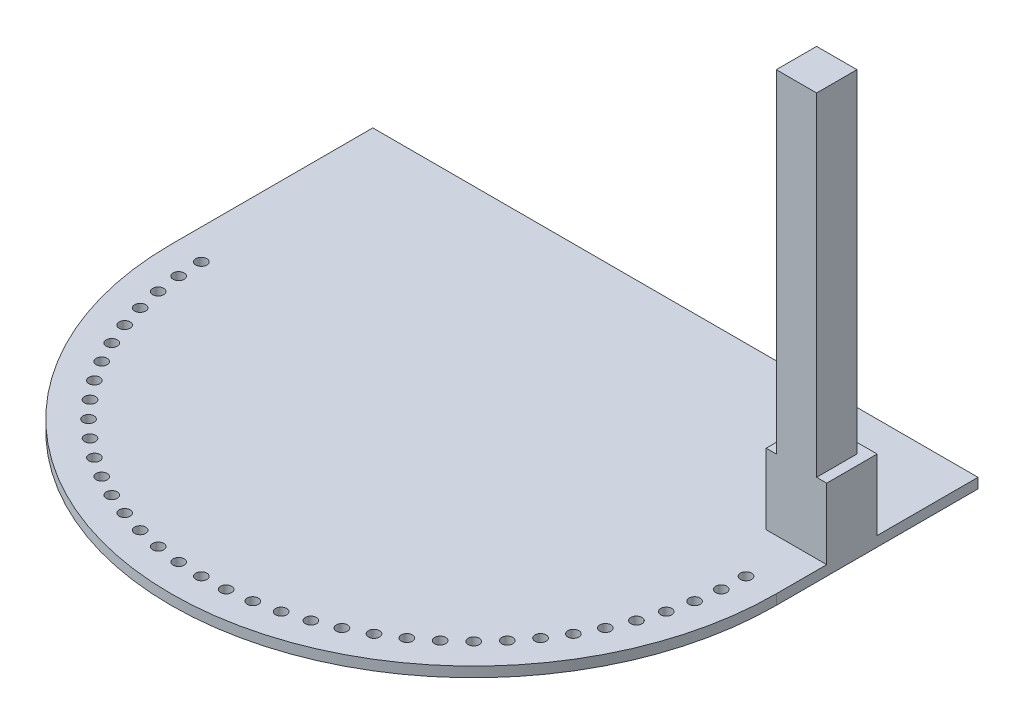
SolidWorks part; units mm, degrees
ref_plane "Front Plane" through (0, 0, 0) normal (0, 0, 1) x (1, 0, 0)
ref_plane "Top Plane" through (0, 0, 0) normal (0, 1, 0) x (1, 0, 0)
ref_plane "Right Plane" through (0, 0, 0) normal (1, 0, 0) x (0, 0, -1)
sketch "Sketch1" plane through (0, 0, 0) normal (0, 1, 0) x (1, 0, 0)
  line L0 (150, 0) -> (-150, 0) construction
  line L2 (-150, 0) -> (-150, 100)
  line L3 (-150, 100) -> (150, 100)
  line L4 (150, 0) -> (150, 100)
  line L5 (0, 100) -> (0, -150) construction
  arc A1 (-150, 0) -> (150, 0) centre (0, 0) ccw
  circle A2 centre (135, 0) radius 2.75
  circle A3 centre (134.4863, -11.766) radius 2.75
  circle A4 centre (132.949, -23.4425) radius 2.75
  circle A5 centre (130.4, -34.9406) radius 2.75
  circle A6 centre (126.8585, -46.1727) radius 2.75
  circle A7 centre (122.3516, -57.0535) radius 2.75
  circle A8 centre (116.9134, -67.5) radius 2.75
  circle A9 centre (110.5855, -77.4328) radius 2.75
  circle A10 centre (103.416, -86.7763) radius 2.75
  circle A11 centre (95.4594, -95.4594) radius 2.75
  circle A12 centre (86.7763, -103.416) radius 2.75
  circle A13 centre (77.4328, -110.5855) radius 2.75
  circle A14 centre (67.5, -116.9134) radius 2.75
  circle A15 centre (57.0535, -122.3516) radius 2.75
  circle A16 centre (46.1727, -126.8585) radius 2.75
  circle A17 centre (34.9406, -130.4) radius 2.75
  circle A18 centre (23.4425, -132.949) radius 2.75
  circle A19 centre (11.766, -134.4863) radius 2.75
  circle A20 centre (0, -135) radius 2.75
  circle A21 centre (-11.766, -134.4863) radius 2.75
  circle A22 centre (-23.4425, -132.949) radius 2.75
  circle A23 centre (-34.9406, -130.4) radius 2.75
  circle A24 centre (-46.1727, -126.8585) radius 2.75
  circle A25 centre (-57.0535, -122.3516) radius 2.75
  circle A26 centre (-67.5, -116.9134) radius 2.75
  circle A27 centre (-77.4328, -110.5855) radius 2.75
  circle A28 centre (-86.7763, -103.416) radius 2.75
  circle A29 centre (-95.4594, -95.4594) radius 2.75
  circle A30 centre (-103.416, -86.7763) radius 2.75
  circle A31 centre (-110.5855, -77.4328) radius 2.75
  circle A32 centre (-116.9134, -67.5) radius 2.75
  circle A33 centre (-122.3516, -57.0535) radius 2.75
  circle A34 centre (-126.8585, -46.1727) radius 2.75
  circle A35 centre (-130.4, -34.9406) radius 2.75
  circle A36 centre (-132.949, -23.4425) radius 2.75
  circle A37 centre (-134.4863, -11.766) radius 2.75
  circle A38 centre (-135, 0) radius 2.75
  point P85 (0, 0)
  dimension "D2" = 300
  dimension "D3" = 37
extrude "Boss-Extrude1" add sketch "Sketch1" along normal blind 5
sketch "Sketch2" plane through (0, 5, 0) normal (0, 1, 0) x (1, 0, 0)
  line L0 (150, 0) -> (150, 100) construction
  line L1 (150, 50) -> (120, 50)
  line L2 (150, 50) -> (150, 25)
  line L3 (150, 25) -> (120, 25)
  line L4 (120, 50) -> (120, 25)
  line L5 (150, 100) -> (-150, 100) construction
  line L11 (125, 25) -> (145, 25)
  line L12 (125, 25) -> (125, 45)
  line L13 (125, 45) -> (145, 45)
  line L14 (145, 25) -> (145, 45)
  line M20 (150, 0) -> (150, 100)
  dimension "D1" = 50
  dimension "D2" = 20
  dimension "D3" = 30
  dimension "D4" = 5
  dimension "D5" = 5
  dimension "D6" = 5
extrude "Boss-Extrude2" add sketch "Sketch2" along normal blind 35 contours L14 L3 L1 L4 L12 L13 M20 region at (149.6095, 5, -37.5)
extrude "Boss-Extrude3" add sketch "Sketch2<3>" along normal blind 200 contours L3 L14 L13 L12 region at (135, 5, -35)
sketch "Sketch2<3>" plane through (0, 5, 0) normal (0, 1, 0) x (1, 0, 0) same geometry as "Sketch2"
